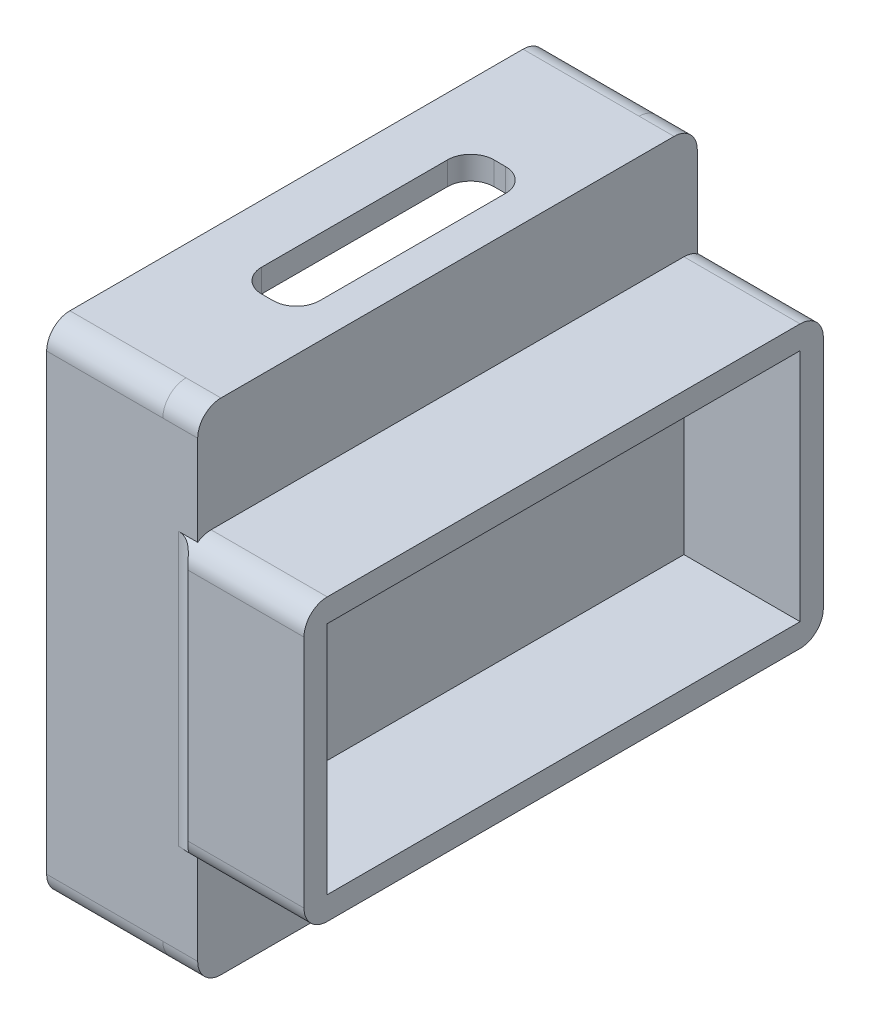
SolidWorks part; units mm, degrees
other "标注1"
sketch "草图13" plane through (-34.5, -21.5, 140) normal (-0.2035, -0.256, 0.945) x (0.0057, 0.9649, 0.2626)
ref_plane "前视基准面" through (0, 0, 0) normal (0, 0, 1) x (1, 0, 0)
ref_plane "上视基准面" through (0, 0, 0) normal (0, 1, 0) x (1, 0, 0)
ref_plane "右视基准面" through (0, 0, 0) normal (1, 0, 0) x (0, 0, -1)
sketch "草图1" plane through (0, 0, 0) normal (0, 0, 1) x (1, 0, 0)
  line L1 (22.5, -19.5) -> (-22.5, -19.5)
  line L2 (22.5, -19.5) -> (22.5, 19.5)
  line L3 (22.5, 19.5) -> (-22.5, 19.5)
  line L4 (-22.5, -19.5) -> (-22.5, 19.5)
  line L5 (22.5, -19.5) -> (-22.5, 19.5) construction
  line L6 (22.5, 19.5) -> (-22.5, -19.5) construction
  point P0 (0, 0)
  dimension "D1" = 45
  dimension "D2" = 39
extrude "拉伸-薄壁1" add sketch "草图1" along normal blind 140 thin thin type one direction wall 2
sketch "草图3" plane through (0, 0, 0) normal (0, 0, -1) x (-1, 0, 0)
  line L1 (-24.5, 21.5) -> (24.5, 21.5)
  line L2 (-24.5, 21.5) -> (-24.5, -21.5)
  line L3 (-24.5, -21.5) -> (24.5, -21.5)
  line L4 (24.5, 21.5) -> (24.5, -21.5)
extrude "凸台-拉伸1" add sketch "草图3" along normal blind 2
sketch "草图4" plane through (-24.5, 0, 0) normal (-1, 0, 0) x (0, 0, 1)
  line L0 (-2, 0) -> (140, 0) construction
  line L1 (-2, -21.5) -> (-2, 21.5) construction
  line L2 (140, 21.5) -> (140, -21.5) construction
  line L3 (140, 21.5) -> (-2, 21.5) construction
  line L4 (90.5, -21.5) -> (47.5, -21.5)
  line L5 (90.5, -21.5) -> (90.5, 21.5)
  line L6 (90.5, 21.5) -> (47.5, 21.5)
  line L7 (47.5, -21.5) -> (47.5, 21.5)
  line L8 (90.5, -21.5) -> (47.5, 21.5) construction
  line L9 (90.5, 21.5) -> (47.5, -21.5) construction
  point P6 (69, 0)
  dimension "D1" = 43
extrude "凸台-拉伸2" add sketch "草图4" along normal blind 10
sketch "草图5" plane through (-34.5, 0, 0) normal (-1, 0, 0) x (0, 0, 1)
  line L0 (47.5, 0) -> (90.5, 0) construction
  line L1 (47.5, 21.5) -> (47.5, -21.5) construction
  line L2 (90.5, -21.5) -> (90.5, 21.5) construction
  line L3 (90.5, 21.5) -> (47.5, 21.5) construction
  line L4 (88.5, -19.5) -> (49.5, -19.5)
  line L5 (88.5, -19.5) -> (88.5, 19.5)
  line L6 (88.5, 19.5) -> (49.5, 19.5)
  line L7 (49.5, -19.5) -> (49.5, 19.5)
  line L8 (88.5, -19.5) -> (49.5, 19.5) construction
  line L9 (88.5, 19.5) -> (49.5, -19.5) construction
  point P6 (69, 0)
  dimension "D1" = 2
  dimension "D2" = 2
extrude "切除-拉伸1" cut sketch "草图5" against normal blind 5
sketch "草图6" plane through (0, 21.5, 0) normal (0, 1, 0) x (1, 0, 0)
  line L0 (-29.5, -47.5) -> (-29.5, -90.5) construction
  line L1 (-34.5, -47.5) -> (-24.5, -47.5) construction
  line L2 (-34.5, -90.5) -> (-24.5, -90.5) construction
  line L3 (-34.5, -90.5) -> (-34.5, -47.5) construction
  line L4 (-24.5, -47.5) -> (-24.5, -90.5) construction
  line L5 (-24.5, -140) -> (-24.5, -90.5) construction
  line L6 (-29.5, -69) -> (-24.5, -69) construction
  line L12 (-24.5, -79) -> (-29.5, -79)
  line L13 (-24.5, -79) -> (-24.5, -59)
  line L14 (-24.5, -59) -> (-29.5, -59)
  line L15 (-29.5, -79) -> (-29.5, -59)
  line L16 (-24.5, -79) -> (-29.5, -59) construction
  line L17 (-24.5, -59) -> (-29.5, -79) construction
  point P15 (-27, -69)
  point P16 (-27, -69)
  dimension "D1" = 5
  dimension "D2" = 20
extrude "切除-拉伸2" cut sketch "草图6" against normal through all
sketch "草图8" plane through (-24.5, 0, 0) normal (-1, 0, 0) x (0, 0, 1)
  line L0 (59, 0) -> (79, 0) construction
  line L1 (59, -21.5) -> (59, 21.5) construction
  line L2 (79, -21.5) -> (79, 21.5) construction
  line L4 (79, -4) -> (59, -4)
  line L5 (79, -4) -> (79, 4)
  line L6 (79, 4) -> (59, 4)
  line L7 (59, -4) -> (59, 4)
  line L8 (79, -4) -> (59, 4) construction
  line L9 (79, 4) -> (59, -4) construction
  point P6 (69, 0)
  dimension "D1" = 8
extrude "凸台-拉伸4" add sketch "草图8" along normal up to surface (5 mm away) up to face at (-29.5, 0, 54.25)
sketch "草图9" plane through (-29.5, 0, 0) normal (-1, 0, 0) x (0, 0, 1)
  line L0 (59, 11.75) -> (79, 11.75) construction
  line L1 (59, 4) -> (59, 19.5) construction
  line L2 (79, 4) -> (79, 21.5) construction
  line L3 (59, 19.5) -> (49.5, 19.5) construction
  line L4 (83.75, 4) -> (54.25, 4)
  line L5 (83.75, 4) -> (83.75, 19.5)
  line L6 (83.75, 19.5) -> (54.25, 19.5)
  line L7 (54.25, 4) -> (54.25, 19.5)
  line L8 (83.75, 4) -> (54.25, 19.5) construction
  line L9 (83.75, 19.5) -> (54.25, 4) construction
  line L10 (59, -11.75) -> (79, -11.75) construction
  line L11 (59, -19.5) -> (59, -4) construction
  line L12 (79, -21.5) -> (79, -4) construction
  line L13 (49.5, 19.5) -> (49.5, -19.5) construction
  line L14 (83.75, -19.5) -> (54.25, -19.5)
  line L15 (83.75, -19.5) -> (83.75, -4)
  line L16 (83.75, -4) -> (54.25, -4)
  line L17 (54.25, -19.5) -> (54.25, -4)
  line L18 (83.75, -19.5) -> (54.25, -4) construction
  line L19 (83.75, -4) -> (54.25, -19.5) construction
  point P6 (69, 11.75)
  point P19 (69, -11.75)
  dimension "D1" = 8
  dimension "D2" = 4.75
extrude "切除-拉伸3" cut sketch "草图9" against normal blind 5
sketch "草图10" plane through (0, -4, 0) normal (0, -1, 0) x (1, 0, 0)
  line L0 (-24.5, 69) -> (-29.5, 69) construction
  line L1 (-24.5, 79) -> (-24.5, 59) construction
  line L2 (-29.5, 59) -> (-29.5, 79) construction
  circle A0 centre (-27, 78.5) radius 1.5
  circle A1 centre (-27, 59.5) radius 1.5
  dimension "D1" = 3
  dimension "D2" = 19
extrude "切除-拉伸4" cut sketch "草图10" against normal blind 3
sketch "草图11" plane through (0, 4, 0) normal (0, 1, 0) x (1, 0, 0)
  circle A0 centre (-27, -59.5) radius 1.5
  circle A1 centre (-27, -78.5) radius 1.5
  dimension "D1" = 3
  dimension "D2" = 3
extrude "切除-拉伸5" cut sketch "草图11" against normal blind 3
fillet "圆角1" radius 2 8 edges at (-29.5, -20.5, 59) (-29.5, -20.5, 79) (-24.5, -20.5, 79) (-24.5, -20.5, 59) (-24.5, 20.5, 59) (-24.5, 20.5, 79) (-29.5, 20.5, 79) (-29.5, 20.5, 59)
sketch "草图12" plane through (-29.5, 0, 0) normal (-1, 0, 0) x (0, 0, 1)
  line L0 (83.75, 4) -> (54.25, 4) construction
  line L1 (74, -4) -> (64, -4)
  line L2 (74, -4) -> (74, 4)
  line L3 (74, 4) -> (64, 4)
  line L4 (64, -4) -> (64, 4)
  line L5 (74, -4) -> (64, 4) construction
  line L6 (74, 4) -> (64, -4) construction
  point P0 (69, 0)
  dimension "D1" = 10
  dimension "D2" = 8
extrude "切除-拉伸6" cut sketch "草图12" against normal up to surface (5 mm away) up to face at (-24.5, 16.125, 69)
fillet "圆角2" radius 2 4 edges at (-32, 19.5, 49.5) (-32, -19.5, 49.5) (-32, -19.5, 88.5) (-32, 19.5, 88.5)
fillet "圆角3" radius 2 4 edges at (-29.5, -21.5, 47.5) (-29.5, -21.5, 90.5) (-29.5, 21.5, 90.5) (-29.5, 21.5, 47.5)
fillet "圆角4" radius 2 8 edges at (-27, 19.5, 83.75) (-27, 4, 83.75) (-27, 4, 54.25) (-27, 19.5, 54.25) (-27, -19.5, 83.75) (-27, -19.5, 54.25) (-27, -4, 54.25) (-27, -4, 83.75)
sketch "草图14" plane through (0, 0, 140) normal (0, 0, 1) x (1, 0, 0)
  line L1 (-24.5, 21.5) -> (24.5, 21.5)
  line L2 (-24.5, 21.5) -> (-24.5, -21.5)
  line L3 (-24.5, -21.5) -> (24.5, -21.5)
  line L4 (24.5, 21.5) -> (24.5, -21.5)
extrude "切除-拉伸7" cut sketch "草图14" against normal through all
sketch "草图15" plane through (-24.5, 0, 0) normal (1, 0, 0) x (0, 0, -1)
  line L0 (-90.5, 0) -> (-47.5, 0) construction
  line L1 (-90.5, -19.5) -> (-90.5, 19.5) construction
  line L2 (-47.5, 19.5) -> (-47.5, -19.5) construction
  line L4 (2, -24.5) -> (-140, -24.5)
  line L5 (2, -24.5) -> (2, 24.5)
  line L6 (2, 24.5) -> (-140, 24.5)
  line L7 (-140, -24.5) -> (-140, 24.5)
  line L8 (2, -24.5) -> (-140, 24.5) construction
  line L9 (2, 24.5) -> (-140, -24.5) construction
  point P6 (-69, 0)
  dimension "D1" = 49
  dimension "D2" = 142
extrude "凸台-拉伸5" add sketch "草图15" along normal blind 43
sketch "草图16" plane through (0, 0, -2) normal (0, 0, -1) x (-1, 0, 0)
  line L0 (-18.5, 0) -> (24.5, 0) construction
  line L1 (-18.5, -24.5) -> (-18.5, 24.5) construction
  line L2 (24.5, 19.5) -> (24.5, -19.5) construction
  line L3 (-18.5, 24.5) -> (24.5, 24.5) construction
  line L4 (21.5, -21.5) -> (-15.5, -21.5)
  line L5 (21.5, -21.5) -> (21.5, 21.5)
  line L6 (21.5, 21.5) -> (-15.5, 21.5)
  line L7 (-15.5, -21.5) -> (-15.5, 21.5)
  line L8 (21.5, -21.5) -> (-15.5, 21.5) construction
  line L9 (21.5, 21.5) -> (-15.5, -21.5) construction
  point P6 (3, 0)
  dimension "D1" = 3
  dimension "D2" = 3
extrude "切除-拉伸8" cut sketch "草图16" against normal offset from surface (139 mm away) 3 up to face at (-3, 0, 140)
sketch "草图17" plane through (0, -24.5, 0) normal (0, -1, 0) x (1, 0, 0)
  line L0 (-24.5, 69) -> (18.5, 69) construction
  line L1 (-24.5, 140) -> (-24.5, -2) construction
  line L2 (18.5, 140) -> (18.5, -2) construction
  line L3 (-3, 140) -> (-3, -2) construction
  line L4 (18.5, 140) -> (-24.5, 140) construction
  line L5 (18.5, -2) -> (-24.5, -2) construction
  line L9 (-12, 112) -> (6, 112)
  line L10 (-12, 118) -> (6, 118)
  line L11 (-12, 115) -> (6, 115) construction
  line L12 (-12, 97) -> (6, 97)
  line L13 (-12, 103) -> (6, 103)
  line L14 (-12, 100) -> (6, 100) construction
  line L15 (-12, 82) -> (6, 82)
  line L16 (-12, 88) -> (6, 88)
  line L17 (-12, 85) -> (6, 85) construction
  line L18 (-12, 67) -> (6, 67)
  line L19 (-12, 73) -> (6, 73)
  line L20 (-12, 70) -> (6, 70) construction
  line L21 (-12, 52) -> (6, 52)
  line L22 (-12, 58) -> (6, 58)
  line L23 (-12, 55) -> (6, 55) construction
  line L24 (-12, 37) -> (6, 37)
  line L25 (-12, 43) -> (6, 43)
  line L26 (-12, 40) -> (6, 40) construction
  line L27 (-12, 22) -> (6, 22)
  line L28 (-12, 28) -> (6, 28)
  line L29 (-12, 25) -> (6, 25) construction
  line L30 (-12, 7) -> (6, 7)
  line L31 (-12, 13) -> (6, 13)
  line L32 (-12, 10) -> (6, 10) construction
  arc A2 (-12, 118) -> (-12, 112) centre (-12, 115) ccw
  arc A3 (6, 112) -> (6, 118) centre (6, 115) ccw
  arc A4 (-12, 103) -> (-12, 97) centre (-12, 100) ccw
  arc A5 (6, 97) -> (6, 103) centre (6, 100) ccw
  arc A6 (-12, 88) -> (-12, 82) centre (-12, 85) ccw
  arc A7 (6, 82) -> (6, 88) centre (6, 85) ccw
  arc A8 (-12, 73) -> (-12, 67) centre (-12, 70) ccw
  arc A9 (6, 67) -> (6, 73) centre (6, 70) ccw
  arc A10 (-12, 58) -> (-12, 52) centre (-12, 55) ccw
  arc A11 (6, 52) -> (6, 58) centre (6, 55) ccw
  arc A12 (-12, 43) -> (-12, 37) centre (-12, 40) ccw
  arc A13 (6, 37) -> (6, 43) centre (6, 40) ccw
  arc A14 (-12, 28) -> (-12, 22) centre (-12, 25) ccw
  arc A15 (6, 22) -> (6, 28) centre (6, 25) ccw
  arc A16 (-12, 13) -> (-12, 7) centre (-12, 10) ccw
  arc A17 (6, 7) -> (6, 13) centre (6, 10) ccw
  point P14 (-3, 130)
  point P23 (-3, 115)
  point P30 (-3, 100)
  point P37 (-3, 85)
  point P44 (-3, 70)
  point P51 (-3, 55)
  point P58 (-3, 40)
  point P65 (-3, 25)
  point P72 (-3, 10)
extrude "切除-拉伸9" cut sketch "草图17" against normal through all
sketch "草图18" plane through (18.5, 0, 0) normal (1, 0, 0) x (0, 0, -1)
  line L0 (-140, 0) -> (2, 0) construction
  line L1 (-140, 24.5) -> (-140, -24.5) construction
  line L2 (2, -24.5) -> (2, 24.5) construction
  line L6 (-118, 12) -> (-118, -12)
  line L7 (-112, 12) -> (-112, -12)
  line L8 (-115, 12) -> (-115, -12) construction
  line L9 (-103, 12) -> (-103, -12)
  line L10 (-97, 12) -> (-97, -12)
  line L11 (-100, 12) -> (-100, -12) construction
  line L12 (-88, 12) -> (-88, -12)
  line L13 (-82, 12) -> (-82, -12)
  line L14 (-85, 12) -> (-85, -12) construction
  line L15 (-73, 12) -> (-73, -12)
  line L16 (-67, 12) -> (-67, -12)
  line L17 (-70, 12) -> (-70, -12) construction
  line L18 (-58, 12) -> (-58, -12)
  line L19 (-52, 12) -> (-52, -12)
  line L20 (-55, 12) -> (-55, -12) construction
  line L21 (-43, 12) -> (-43, -12)
  line L22 (-37, 12) -> (-37, -12)
  line L23 (-40, 12) -> (-40, -12) construction
  line L24 (-28, 12) -> (-28, -12)
  line L25 (-22, 12) -> (-22, -12)
  line L26 (-25, 12) -> (-25, -12) construction
  line L27 (-13, 12) -> (-13, -12)
  line L28 (-7, 12) -> (-7, -12)
  line L29 (-10, 12) -> (-10, -12) construction
  arc A2 (-112, 12) -> (-118, 12) centre (-115, 12) ccw
  arc A3 (-118, -12) -> (-112, -12) centre (-115, -12) ccw
  arc A4 (-97, 12) -> (-103, 12) centre (-100, 12) ccw
  arc A5 (-103, -12) -> (-97, -12) centre (-100, -12) ccw
  arc A6 (-82, 12) -> (-88, 12) centre (-85, 12) ccw
  arc A7 (-88, -12) -> (-82, -12) centre (-85, -12) ccw
  arc A8 (-67, 12) -> (-73, 12) centre (-70, 12) ccw
  arc A9 (-73, -12) -> (-67, -12) centre (-70, -12) ccw
  arc A10 (-52, 12) -> (-58, 12) centre (-55, 12) ccw
  arc A11 (-58, -12) -> (-52, -12) centre (-55, -12) ccw
  arc A12 (-37, 12) -> (-43, 12) centre (-40, 12) ccw
  arc A13 (-43, -12) -> (-37, -12) centre (-40, -12) ccw
  arc A14 (-22, 12) -> (-28, 12) centre (-25, 12) ccw
  arc A15 (-28, -12) -> (-22, -12) centre (-25, -12) ccw
  arc A16 (-7, 12) -> (-13, 12) centre (-10, 12) ccw
  arc A17 (-13, -12) -> (-7, -12) centre (-10, -12) ccw
  point P8 (-130, 0)
  point P16 (-115, 0)
  point P23 (-100, 0)
  point P30 (-85, 0)
  point P37 (-70, 0)
  point P44 (-55, 0)
  point P51 (-40, 0)
  point P58 (-25, 0)
  point P65 (-10, 0)
extrude "切除-拉伸10" cut sketch "草图18" against normal blind 10
sketch "草图19" plane through (-24.5, 0, 0) normal (-1, 0, 0) x (0, 0, 1)
  line L0 (-2, 0) -> (140, 0) construction
  line L1 (-2, -24.5) -> (-2, 24.5) construction
  line L2 (140, 24.5) -> (140, -24.5) construction
  line L3 (8, 12) -> (8, -12) construction
  line L4 (11, 12) -> (11, -12)
  line L5 (5, 12) -> (5, -12)
  line L6 (20, 12) -> (20, -12)
  line L7 (26, 12) -> (26, -12)
  line L8 (23, 12) -> (23, -12) construction
  line L9 (35, 12) -> (35, -12)
  line L10 (41, 12) -> (41, -12)
  line L11 (38, 12) -> (38, -12) construction
  arc A0 (11, 12) -> (5, 12) centre (8, 12) ccw
  arc A1 (5, -12) -> (11, -12) centre (8, -12) ccw
  arc A2 (26, 12) -> (20, 12) centre (23, 12) ccw
  arc A3 (20, -12) -> (26, -12) centre (23, -12) ccw
  arc A4 (41, 12) -> (35, 12) centre (38, 12) ccw
  arc A5 (35, -12) -> (41, -12) centre (38, -12) ccw
  point P8 (8, 0)
  point P16 (23, 0)
  point P23 (38, 0)
  dimension "D4" = 3
  dimension "D1" = 12
  dimension "D2" = 12
  dimension "D3" = 10
  dimension "D5" = 3
extrude "切除-拉伸11" cut sketch "草图19" against normal blind 10
sketch "草图21" plane through (-24.5, 0, 0) normal (-1, 0, 0) x (0, 0, 1)
  line L0 (140, 0) -> (-2, 0) construction
  line L1 (140, 24.5) -> (140, -24.5) construction
  line L2 (-2, -24.5) -> (-2, 24.5) construction
  line L6 (112, 12) -> (112, -12)
  line L7 (118, 12) -> (118, -12)
  line L8 (115, 12) -> (115, -12) construction
  line L9 (97, 12) -> (97, -12)
  line L10 (103, 12) -> (103, -12)
  line L11 (100, 12) -> (100, -12) construction
  arc A2 (118, 12) -> (112, 12) centre (115, 12) ccw
  arc A3 (112, -12) -> (118, -12) centre (115, -12) ccw
  arc A4 (103, 12) -> (97, 12) centre (100, 12) ccw
  arc A5 (97, -12) -> (103, -12) centre (100, -12) ccw
  point P8 (130, 0)
  point P16 (115, 0)
  point P23 (100, 0)
extrude "切除-拉伸12" cut sketch "草图21" against normal blind 10
fillet "圆角5" radius 2 4 edges at (-24.5, -24.5, 69) (18.5, -24.5, 69) (18.5, 24.5, 69) (-24.5, 24.5, 69)
sketch "草图22" plane through (-24.5, 0, 0) normal (-1, 0, 0) x (0, 0, 1)
  line L0 (-2, 24.5) -> (140, 24.5) construction
  line L1 (47.5, 24.5) -> (-8.4029, 24.5)
  line L2 (47.5, 24.5) -> (47.5, -28.4937)
  line L3 (47.5, -28.4937) -> (-8.4029, -28.4937)
  line L4 (-8.4029, 24.5) -> (-8.4029, -28.4937)
  line L5 (140, -24.5) -> (-2, -24.5) construction
  line L6 (90.5, -24.5) -> (153.8935, -24.5)
  line L7 (90.5, -24.5) -> (90.5, 36.1311)
  line L8 (90.5, 36.1311) -> (153.8935, 36.1311)
  line L9 (153.8935, -24.5) -> (153.8935, 36.1311)
extrude "切除-拉伸13" cut sketch "草图22" against normal through all
sketch "草图24" plane through (-24.5, 0, 0) normal (-1, 0, 0) x (0, 0, 1)
  line L1 (47.5, 21.5) -> (95.629, 21.5)
  line L2 (47.5, 21.5) -> (47.5, 26.5634)
  line L3 (47.5, 26.5634) -> (95.629, 26.5634)
  line L4 (95.629, 21.5) -> (95.629, 26.5634)
  line L5 (47.5, -21.5) -> (98.3181, -21.5)
  line L6 (47.5, -21.5) -> (47.5, -26.4978)
  line L7 (47.5, -26.4978) -> (98.3181, -26.4978)
  line L8 (98.3181, -21.5) -> (98.3181, -26.4978)
extrude "切除-拉伸14" cut sketch "草图24" against normal through all
sketch "草图25" plane through (0, 21.5, 0) normal (0, 1, 0) x (1, 0, 0)
  line L1 (8.5765, -43.3755) -> (28.8137, -43.3755)
  line L2 (8.5765, -43.3755) -> (8.5765, -92.6215)
  line L3 (8.5765, -92.6215) -> (28.8137, -92.6215)
  line L4 (28.8137, -43.3755) -> (28.8137, -92.6215)
extrude "切除-拉伸15" cut sketch "草图25" against normal through all
fillet "圆角6" radius 2 4 edges at (-23, 21.5, 47.5) (-23, -21.5, 47.5) (-23, -21.5, 90.5) (-23, 21.5, 90.5)
sketch "草图26" plane through (-21.5, 0, 0) normal (1, 0, 0) x (0, 0, -1)
  line L0 (-90.5, 0) -> (-47.5, 0) construction
  line L1 (-90.5, 19.5) -> (-90.5, -19.5) construction
  line L2 (-47.5, -19.5) -> (-47.5, 19.5) construction
  line L4 (-46.65, -12.1) -> (-91.35, -12.1)
  line L5 (-46.65, -12.1) -> (-46.65, 12.1)
  line L6 (-46.65, 12.1) -> (-91.35, 12.1)
  line L7 (-91.35, -12.1) -> (-91.35, 12.1)
  line L8 (-46.65, -12.1) -> (-91.35, 12.1) construction
  line L9 (-46.65, 12.1) -> (-91.35, -12.1) construction
  line L10 (-48.65, -10.1) -> (-89.35, -10.1)
  line L11 (-48.65, -10.1) -> (-48.65, 10.1)
  line L12 (-48.65, 10.1) -> (-89.35, 10.1)
  line L13 (-89.35, -10.1) -> (-89.35, 10.1)
  line L14 (-48.65, -10.1) -> (-89.35, 10.1) construction
  line L15 (-48.65, 10.1) -> (-89.35, -10.1) construction
  point P6 (-69, 0)
  point P11 (-69, 0)
  dimension "D1" = 24.2
  dimension "D2" = 44.7
  dimension "D3" = 20.2
  dimension "D4" = 40.7
extrude "凸台-拉伸6" add sketch "草图26" along normal blind 10
fillet "圆角7" radius 2 2 edges at (-21.5, 0, 90.5) (-21.5, 0, 47.5)
fillet "圆角8" radius 2 4 edges at (-16.5, 12.1, 46.65) (-16.5, -12.1, 46.65) (-16.5, -12.1, 91.35) (-16.5, 12.1, 91.35)
